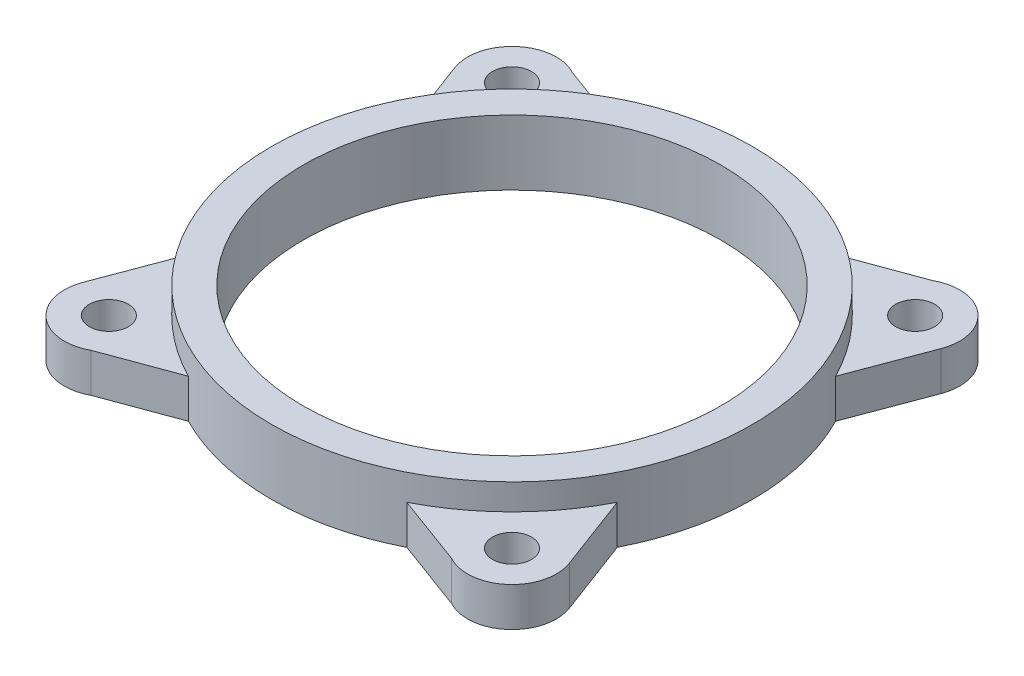
SolidWorks part; units mm, degrees
ref_plane "Front Plane" through (0, 0, 0) normal (0, 0, 1) x (1, 0, 0)
ref_plane "Top Plane" through (0, 0, 0) normal (0, 1, 0) x (1, 0, 0)
ref_plane "Right Plane" through (0, 0, 0) normal (1, 0, 0) x (0, 0, -1)
sketch "Sketch2" plane through (0, 9, 0) normal (0, 1, 0) x (1, 0, 0)
  circle A0 centre (-0.5, 0) radius 18.5 construction
  circle A7 centre (-0.5, 0) radius 18.5
  circle A15 centre (-0.5, 0) radius 16.05
  dimension "D1" = 37
  dimension "D2" = 32.1
extrude "Boss-Extrude1" add sketch "Sketch2" along normal blind 5
sketch "Sketch3" plane through (0, 9, 0) normal (0, -1, 0) x (1, 0, 0)
  line L8 (13.3573, 18.5) -> (7.8938, 16.4862)
  line L9 (15.9862, 8.3938) -> (18.2022, 14.2982)
  line L10 (18.2022, -14.2982) -> (15.9862, -8.3938)
  line L11 (7.8938, -16.4862) -> (13.3573, -18.5)
  line L12 (-14.3573, -18.5) -> (-8.8938, -16.4862)
  line L13 (-16.9862, -8.3938) -> (-19.2022, -14.2982)
  line L14 (-19.2022, 14.2982) -> (-16.9862, 8.3938)
  line L15 (-8.8938, 16.4862) -> (-14.3573, 18.5)
  line L16 (13.3573, 18.5) -> (7.8938, 16.4862)
  line L17 (15.9862, 8.3938) -> (18.2022, 14.2982)
  line L18 (18.2022, -14.2982) -> (15.9862, -8.3938)
  line L19 (7.8938, -16.4862) -> (13.3573, -18.5)
  line L20 (-14.3573, -18.5) -> (-8.8938, -16.4862)
  line L21 (-16.9862, -8.3938) -> (-19.2022, -14.2982)
  line L22 (-19.2022, 14.2982) -> (-16.9862, 8.3938)
  line L23 (-8.8938, 16.4862) -> (-14.3573, 18.5)
  arc A0 (15.9862, -8.3938) -> (7.8938, -16.4862) centre (-0.5, 0) cw
  arc A1 (-8.8938, -16.4862) -> (-16.9862, -8.3938) centre (-0.5, 0) cw
  arc A2 (15.9862, 8.3938) -> (7.8938, 16.4862) centre (-0.5, 0) ccw
  arc A3 (-8.8938, 16.4862) -> (-16.9862, 8.3938) centre (-0.5, 0) ccw
  circle A4 centre (-16, 15.5) radius 1.5
  circle A5 centre (15, 15.5) radius 1.5
  circle A6 centre (15, -15.5) radius 1.5
  circle A7 centre (-16, -15.5) radius 1.5
  arc A8 (7.8938, 16.4862) -> (-8.8938, 16.4862) centre (-0.5, 0) ccw
  arc A9 (18.2022, 14.2982) -> (13.3573, 18.5) centre (15, 15.5) ccw
  arc A10 (15.9862, -8.3938) -> (15.9862, 8.3938) centre (-0.5, 0) ccw
  arc A11 (13.3573, -18.5) -> (18.2022, -14.2982) centre (15, -15.5) ccw
  arc A12 (-8.8938, -16.4862) -> (7.8938, -16.4862) centre (-0.5, 0) ccw
  arc A13 (-19.2022, -14.2982) -> (-14.3573, -18.5) centre (-16, -15.5) ccw
  arc A14 (-16.9862, 8.3938) -> (-16.9862, -8.3938) centre (-0.5, 0) ccw
  arc A15 (-14.3573, 18.5) -> (-19.2022, 14.2982) centre (-16, 15.5) ccw
  arc A17 (18.2022, 14.2982) -> (13.3573, 18.5) centre (15, 15.5) ccw
  arc A19 (13.3573, -18.5) -> (18.2022, -14.2982) centre (15, -15.5) ccw
  arc A21 (-19.2022, -14.2982) -> (-14.3573, -18.5) centre (-16, -15.5) ccw
  arc A23 (-14.3573, 18.5) -> (-19.2022, 14.2982) centre (-16, 15.5) ccw
  circle M17 centre (-0.5, 0) radius 18.5
  dimension "D1" = 0
extrude "Boss-Extrude2" add sketch "Sketch3" against normal blind 3 contours L21 A21 L20 A7 M17 | L19 A19 L18 A6 M17 | L17 A17 L16 A5 M17 | L23 A23 L22 A4 M17 region at (17.1434, 9, 17.9715) region at (-13.6867, 9, 13.1867) region at (16.9548, 9, -11.3983) region at (-13.6867, 9, -13.1867)
